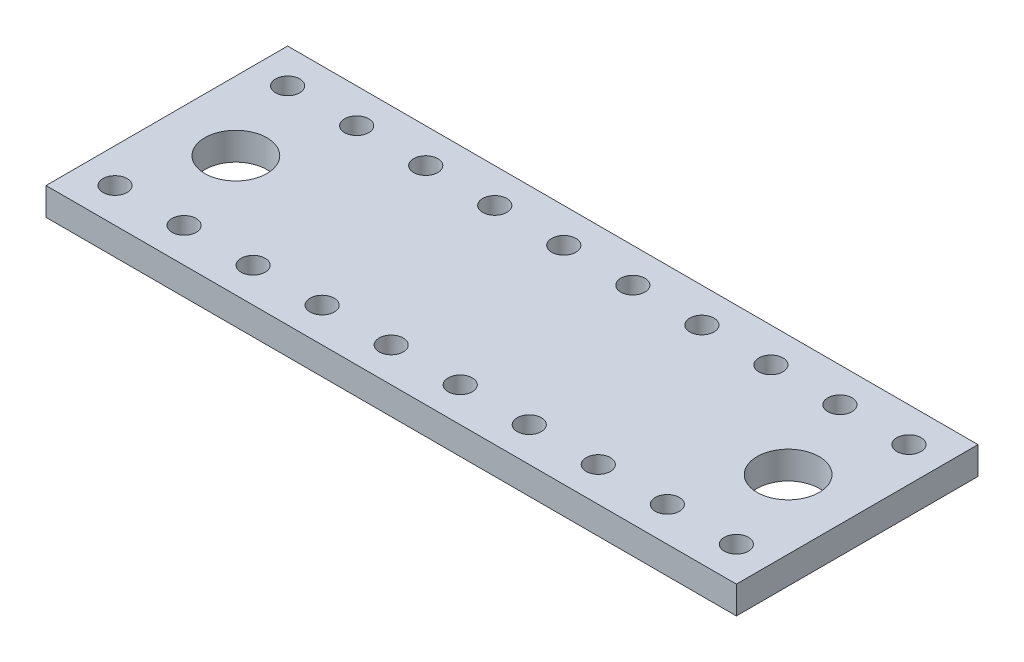
SolidWorks part; units mm, degrees
material "Plain Carbon Steel"
ref_plane "Front Plane" through (0, 0, 0) normal (0, 0, 1) x (1, 0, 0)
ref_plane "Top Plane" through (0, 0, 0) normal (0, 1, 0) x (1, 0, 0)
ref_plane "Right Plane" through (0, 0, 0) normal (1, 0, 0) x (0, 0, -1)
sketch "Sketch1" plane through (0, 0, 0) normal (0, 1, 0) x (1, 0, 0)
  line L1 (0, 0) -> (100, 0)
  line L2 (0, 0) -> (0, 35)
  line L3 (0, 35) -> (100, 35)
  line L4 (100, 0) -> (100, 35)
  dimension "D1" = 100
  dimension "D2" = 35
extrude "Boss-Extrude1" add sketch "Sketch1" along normal blind 4
ref_plane "Plane1" through (0, 0, -17.5) normal (0, 0, -1) x (-1, 0, 0)
ref_plane "Plane2" through (50, 0, 0) normal (1, 0, 0) x (0, 0, -1)
sketch "Sketch2" plane through (0, 4, 0) normal (0, 1, 0) x (1, 0, 0)
  line L0 (5, 30) -> (5, 35) construction
  line L3 (100, 35) -> (0, 35) construction
  line L4 (5, 30) -> (0, 30) construction
  line L5 (0, 35) -> (0, 0) construction
  line L6 (10, 17.5) -> (0, 17.5) construction
  line L7 (50, 35) -> (50, 0)
  line L8 (0, 0) -> (100, 0) construction
  circle A0 centre (10, 17.5) radius 4.5
  circle A1 centre (5, 30) radius 1.75
  dimension "D1" = 9
  dimension "D2" = 3.5
  dimension "D3" = 5
  dimension "D5" = 10
extrude "Cut-Extrude1" cut sketch "Sketch2" against normal through all both and the other way through all contours A1 region at (5, 4, -30)
pattern_linear "LPattern1" count 10 spacing 10 along (1, 0, 0) of "Cut-Extrude1"
mirror "Mirror1" about plane through (0, 0, -17.5) normal (0, 0, -1) of "LPattern1"
sketch "Sketch4" plane through (0, 4, 0) normal (0, 1, 0) x (1, 0, 0)
  line L0 (2.2, 17.5) -> (-2.2, 17.5) construction
  line L1 (50, 17.5) -> (50, 35) construction
  line L2 (100, 35) -> (0, 35) construction
  circle A0 centre (50, 17.5) radius 2.5
  dimension "D1" = 5
extrude "Cut-Extrude3" cut sketch "Sketch2<3>" against normal blind 4 contours A0 region at (10, 4, -17.5)
sketch "Sketch2<3>" plane through (0, 4, 0) normal (0, 1, 0) x (1, 0, 0) same geometry as "Sketch2"
mirror "Mirror2" about plane through (50, 0, 0) normal (1, 0, 0) of "Cut-Extrude3"
ref_plane "midplane" through (50, 0, 0) normal (-1, 0, 0) x (0, 0, 1)
